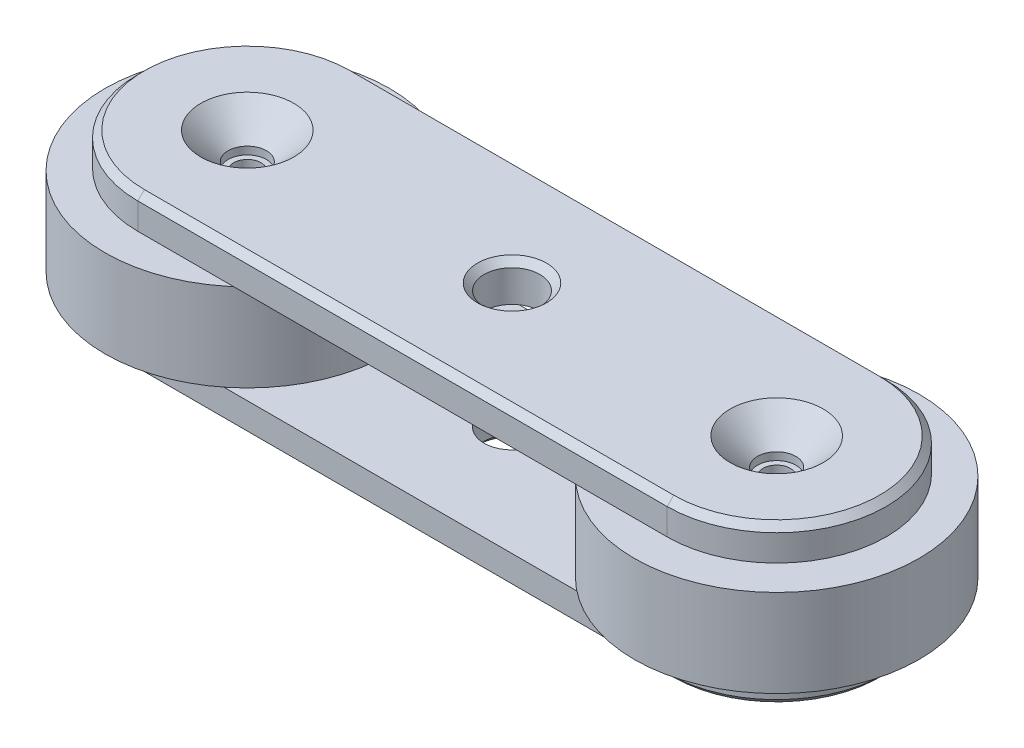
SolidWorks part; units mm, degrees
other "Rotor_1"
other "Rotor_2" parameters "D1"=10.994, "D3"=11.0231, "D4"=5, "D2"=144
ref_plane "Front Plane" through (0, 0, 0) normal (0, 0, 1) x (1, 0, 0)
ref_plane "Top Plane" through (0, 0, 0) normal (0, 1, 0) x (1, 0, 0)
ref_plane "Right Plane" through (0, 0, 0) normal (1, 0, 0) x (0, 0, -1)
sketch "Sketch1" plane through (0, 0, 0) normal (0, 1, 0) x (1, 0, 0)
  line L0 (24.175, 0) -> (-24.175, 0) construction
  line L1 (24.175, -10) -> (-24.175, -10)
  line L2 (24.175, 10) -> (-24.175, 10)
  arc A0 (24.175, -10) -> (24.175, 10) centre (24.175, 0) ccw
  arc A1 (-24.175, 10) -> (-24.175, -10) centre (-24.175, 0) ccw
  circle A2 centre (0, 0) radius 2.55
  circle A3 centre (-24.175, 0) radius 5 construction
  circle A4 centre (24.175, 0) radius 5 construction
  point P2 (0, 0)
  dimension "D1" = 10
  dimension "D3" = 5.1
  dimension "D4" = 10
  dimension "D2" = 48.35
extrude "Boss-Extrude1" add sketch "Sketch1" along normal blind 3
sketch "Sketch10" plane through (0, 3, 0) normal (0, 1, 0) x (1, 0, 0)
  circle A0 centre (-24.175, 0) radius 7.5
  circle A1 centre (24.175, 0) radius 7.5
  dimension "D1" = 15
extrude "Boss-Extrude6" add sketch "Sketch10" along normal blind 0.2
sketch "Sketch11" plane through (0, 3.2, 0) normal (0, 1, 0) x (1, 0, 0)
  circle A0 centre (-24.175, 0) radius 5.05
  circle A1 centre (24.175, 0) radius 5.05
  dimension "D1" = 10.1
extrude "Boss-Extrude8" add sketch "Sketch11" along normal blind 8
sketch "Sketch12" plane through (0, 3.2, 0) normal (0, 1, 0) x (1, 0, 0)
  circle A0 centre (-24.175, 0) radius 5
  circle A1 centre (-24.175, 0) radius 13
  dimension "D1" = 26
  dimension "D2" = 10
extrude "Boss-Extrude9" add sketch "Sketch12" along normal blind 8 separate body
mirror "Mirror3" about plane through (0, 0, 0) normal (1, 0, 0) of bodies 113
sketch "Sketch13" plane through (0, 11.2, 0) normal (0, 1, 0) x (1, 0, 0)
  circle A0 centre (-24.175, 0) radius 1.25
  circle A1 centre (24.175, 0) radius 1.25
  dimension "D1" = 2.5
extrude "Cut-Extrude6" cut sketch "Sketch13" against normal through all
ref_plane "Plane1" through (0, 11.4, 0) normal (0, 1, 0) x (1, 0, 0)
sketch "Sketch14" plane through (0, 11.4, 0) normal (0, 1, 0) x (1, 0, 0)
  line L2 (-24.175, -10) -> (24.175, -10)
  line L3 (24.175, 10) -> (-24.175, 10)
  line L4 (-24.175, -10) -> (24.175, -10)
  line L5 (24.175, 10) -> (-24.175, 10)
  circle A0 centre (0, 0) radius 2.55 construction
  circle A1 centre (0, 0) radius 2.55
  arc A2 (24.175, -10) -> (24.175, 10) centre (24.175, 0) ccw
  arc A3 (-24.175, 10) -> (-24.175, -10) centre (-24.175, 0) ccw
  arc A4 (24.175, -10) -> (24.175, 10) centre (24.175, 0) ccw
  arc A5 (-24.175, 10) -> (-24.175, -10) centre (-24.175, 0) ccw
  circle A8 centre (-24.175, 0) radius 1.75
  circle A9 centre (24.175, 0) radius 1.75
  dimension "D2" = 3.5
  dimension "D1" = 0
extrude "Boss-Extrude10" add sketch "Sketch14" along normal blind 3 separate body
sketch "Sketch15" plane through (0, 11.4, 0) normal (0, -1, 0) x (1, 0, 0)
  circle A2 centre (24.175, 0) radius 7.5 construction
  circle A3 centre (-24.175, 0) radius 7.5 construction
  circle A4 centre (-24.175, 0) radius 1.75 construction
  circle A5 centre (24.175, 0) radius 1.75 construction
  circle A6 centre (24.175, 0) radius 7.5
  circle A7 centre (-24.175, 0) radius 7.5
  circle A8 centre (-24.175, 0) radius 1.75
  circle A9 centre (24.175, 0) radius 1.75
extrude "Boss-Extrude11" add sketch "Sketch15" along normal blind 0.2
chamfer "Chamfer1" distance 2.5 angle 45 2 edges at (-24.175, 14.4, 1.75) (24.175, 14.4, 1.75)
chamfer "Chamfer2" distance 0.6 angle 45 5 edges at (0, 14.4, 10) (34.175, 14.4, 0) (-34.175, 14.4, 0) (0, 14.4, -10) (0, 14.4, 2.55)
sketch "Sketch16" plane through (0, 3, 0) normal (0, 1, 0) x (1, 0, 0)
  line L0 (-10, 0) -> (-2.55, 0)
  line L1 (2.55, 0) -> (10, 0)
  arc A0 (10, 0) -> (-10, 0) centre (0, 0) ccw
  circle A1 centre (0, 0) radius 2.55 construction
  arc A2 (2.55, 0) -> (-2.55, 0) centre (0, 0) ccw
  dimension "D1" = 20
extrude "Boss-Extrude12" add sketch "Sketch16" along normal blind 0.5
sketch "Sketch17" plane through (0, 11.4, 0) normal (0, -1, 0) x (1, 0, 0)
  line L4 (-2.55, 0) -> (-10, 0)
  line L5 (10, 0) -> (2.55, 0)
  line L6 (-2.55, 0) -> (-10, 0)
  line L7 (10, 0) -> (2.55, 0)
  arc A5 (-10, 0) -> (10, 0) centre (0, 0) ccw
  arc A6 (-2.55, 0) -> (2.55, 0) centre (0, 0) ccw
  arc A8 (-10, 0) -> (10, 0) centre (0, 0) ccw
  arc A9 (-2.55, 0) -> (2.55, 0) centre (0, 0) ccw
  dimension "D1" = 0
extrude "Boss-Extrude13" add sketch "Sketch17" along normal blind 0.5
chamfer "Chamfer3" distance 0.6 angle 45 7 edges at (24.175, 0, 1.25) (0, 0, 2.55) (-24.175, 0, 1.25) (34.175, 0, 0) (0, 0, -10) (0, 0, 10) (-34.175, 0, 0)
delete or keep bodies "Body-Delete/Keep 1" [suppressed] type delete bodies bodies 118
delete or keep bodies "Body-Delete/Keep 2" [suppressed] type delete bodies bodies 119
equation "\"D2@Sketch1\"=74.35-26"
